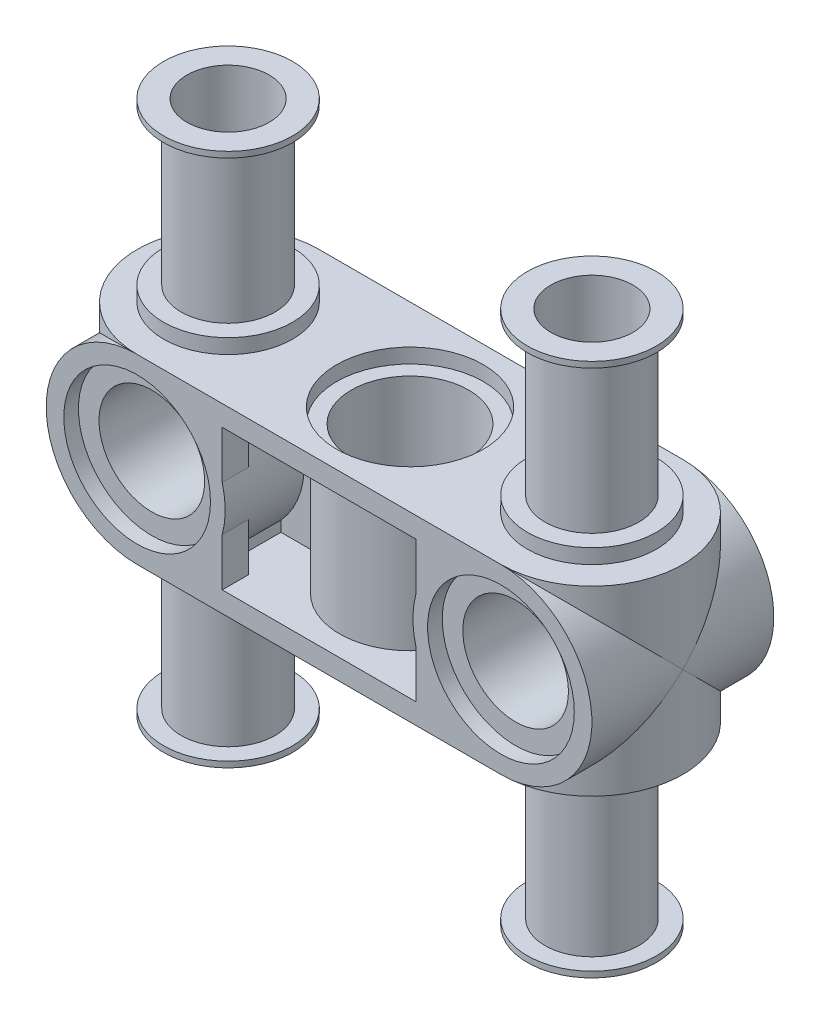
SolidWorks part; units mm, degrees
material "PVC Rigid"
ref_plane "Front Plane" through (0, 0, 0) normal (0, 0, 1) x (1, 0, 0)
ref_plane "Top Plane" through (0, 0, 0) normal (0, 1, 0) x (1, 0, 0)
ref_plane "Right Plane" through (0, 0, 0) normal (1, 0, 0) x (0, 0, -1)
sketch "Sketch1" plane through (0, 0, 0) normal (0, 1, 0) x (1, 0, 0)
  line L0 (-19.2625, 0) -> (26.4221, 0) construction
  line L1 (-7.874, 3.937) -> (7.874, 3.937)
  line L2 (0, 0) -> (0, 11.754) construction
  line L3 (7.874, -3.937) -> (-7.874, -3.937)
  circle A0 centre (-7.874, 0) radius 2.54 construction
  circle A1 centre (0, 0) radius 2.54 construction
  circle A2 centre (7.874, 0) radius 2.54 construction
  arc A3 (7.874, -3.937) -> (7.874, 3.937) centre (7.874, 0) ccw
  arc A4 (-7.874, 3.937) -> (-7.874, -3.937) centre (-7.874, 0) ccw
  dimension "D3" = 5.08
  dimension "D4" = 7.874
  dimension "D1" = 7.874
  dimension "D2" = 7.874
extrude "Extrude1" add sketch "Sketch1" along normal blind 3.937
sketch "Sketch2" plane through (0, 0, 0) normal (0, -1, 0) x (1, 0, 0)
  circle A0 centre (0, 0) radius 2.794
  dimension "D1" = 5.588
extrude "Cut-Extrude1" cut sketch "Sketch2" against normal blind 0.254
sketch "Sketch3" plane through (0, 0, 0) normal (0, -1, 0) x (1, 0, 0)
  circle A0 centre (7.874, 0) radius 2.794
  circle A1 centre (-7.874, 0) radius 2.794
  arc A2 (-7.874, 3.937) -> (-7.874, -3.937) centre (-7.874, 0) ccw construction
  arc A3 (7.874, -3.937) -> (7.874, 3.937) centre (7.874, 0) ccw construction
  dimension "D1" = 5.588
extrude "Extrude2" add sketch "Sketch3" along normal blind 0.635
sketch "Sketch5" plane through (0, -0.635, 0) normal (0, -1, 0) x (1, 0, 0)
  circle A0 centre (7.874, 0) radius 2.794 construction
  circle A1 centre (7.874, 0) radius 2.032
  circle A2 centre (-7.874, 0) radius 2.794 construction
  circle A3 centre (7.874, 0) radius 1.778
  circle A4 centre (-7.874, 0) radius 2.032
  circle A8 centre (-7.874, 0) radius 1.778
  dimension "D2" = 4.064
  dimension "D1" = 3.556
extrude "Extrude4" add sketch "Sketch5" along normal blind 6.985
sketch "Sketch6" plane through (0, -7.62, 0) normal (0, -1, 0) x (1, 0, 0)
  circle A1 centre (-7.874, 0) radius 1.778 construction
  circle A3 centre (7.874, 0) radius 1.778 construction
  circle A4 centre (-7.874, 0) radius 2.794 construction
  circle A5 centre (7.874, 0) radius 2.794 construction
  circle A6 centre (-7.874, 0) radius 2.794
  circle A7 centre (7.874, 0) radius 2.794
  circle A8 centre (7.874, 0) radius 1.778
  circle A9 centre (-7.874, 0) radius 1.778
extrude "Extrude5" add sketch "Sketch6" against normal blind 0.254
sketch "Sketch7" plane through (0, 0, -3.937) normal (0, 0, -1) x (-1, 0, 0)
  line L0 (-7.874, 3.937) -> (7.874, 3.937) construction
  line L2 (-7.874, 0) -> (7.874, 0) construction
  line L3 (-7.874, 0) -> (7.874, 0)
  line L4 (-7.874, 3.937) -> (7.874, 3.937)
  line L5 (-7.874, 3.937) -> (-11.811, 3.937)
  line L6 (7.874, 3.937) -> (11.811, 3.937)
  arc A0 (-11.811, 3.937) -> (-7.874, 0) centre (-7.874, 3.937) ccw
  arc A1 (7.874, 0) -> (11.811, 3.937) centre (7.874, 3.937) ccw
extrude "Extrude6" add sketch "Sketch7" against normal blind 7.874
sketch "Sketch8" plane through (0, 3.937, 0) normal (0, 1, 0) x (1, 0, 0)
  circle A0 centre (-7.874, 0) radius 2.54 construction
  circle A1 centre (0, 0) radius 2.54 construction
  circle A2 centre (7.874, 0) radius 2.54 construction
  circle A3 centre (-7.874, 0) radius 2.54 construction
  circle A4 centre (0, 0) radius 2.54
  circle A5 centre (7.874, 0) radius 2.54 construction
extrude "Cut-Extrude2" cut sketch "Sketch8" against normal blind 3.556
sketch "Sketch9" plane through (0, 0, 3.937) normal (0, 0, 1) x (1, 0, 0)
  circle A0 centre (7.874, 3.937) radius 2.286
  circle A1 centre (-7.874, 3.937) radius 2.286
  dimension "D1" = 4.572
extrude "Cut-Extrude3" cut sketch "Sketch9" against normal through all
sketch "Sketch10" plane through (0, 0, 3.937) normal (0, 0, 1) x (1, 0, 0)
  circle A0 centre (7.874, 3.937) radius 3.175
  circle A1 centre (-7.874, 3.937) radius 3.175
  dimension "D1" = 6.35
extrude "Cut-Extrude4" cut sketch "Sketch10" against normal blind 0.635
mirror "Mirror2" about plane through (0, 0, 0) normal (0, 0, 1) of "Cut-Extrude4"
sketch "Sketch11" plane through (0, 3.937, 0) normal (0, 1, 0) x (1, 0, 0)
  line L0 (-5.08, -0.508) -> (-5.08, -2.794)
  line L1 (5.08, 0.508) -> (5.08, 2.794)
  line L2 (5.08, -2.794) -> (5.08, -0.508)
  line L15 (-4.191, -3.429) -> (4.191, -3.429)
  line L23 (4.699, 3.937) -> (-4.699, 3.937) construction
  line L24 (-5.809, 0) -> (6.5071, 0) construction
  line L25 (-5.08, 0.508) -> (-3.0054, 0.508)
  line L26 (-5.809, 0.508) -> (6.5071, 0.508) construction
  line L27 (-5.08, -0.508) -> (-3.0054, -0.508)
  line L28 (-5.809, -0.508) -> (6.5071, -0.508) construction
  line L29 (-4.699, -3.937) -> (4.699, -3.937) construction
  line L30 (-4.191, -3.937) -> (4.191, -3.937)
  line L31 (3.0054, -0.508) -> (5.08, -0.508)
  line L32 (-4.191, -2.794) -> (-4.191, -3.429)
  line L34 (4.191, -3.429) -> (4.191, -2.794)
  line L35 (4.191, -2.794) -> (5.08, -2.794)
  line L36 (5.08, -2.794) -> (5.08, 2.794)
  line L37 (4.191, 3.429) -> (-4.191, 3.429)
  line L38 (4.191, 3.937) -> (-4.191, 3.937)
  line L39 (-4.191, 3.429) -> (-4.191, 2.794)
  line L40 (-5.08, 2.794) -> (-5.08, -2.794)
  line L41 (-5.08, -2.794) -> (-4.191, -2.794)
  line L42 (-4.191, -2.794) -> (-4.191, -3.937)
  line L43 (3.0054, 0.508) -> (5.08, 0.508)
  line L44 (4.191, -3.937) -> (4.191, -2.794)
  line L45 (4.191, -2.794) -> (5.08, -2.794)
  line L47 (-4.191, 3.937) -> (-4.191, 2.794)
  line L49 (-4.191, 2.794) -> (-5.08, 2.794)
  line L50 (-5.08, 2.794) -> (-5.08, 0.508)
  line L51 (-5.08, -2.794) -> (-4.191, -2.794)
  line L65 (-4.191, 2.794) -> (-5.08, 2.794)
  line L70 (5.08, 2.794) -> (4.191, 2.794)
  line L71 (5.08, 2.794) -> (4.191, 2.794)
  line L72 (4.191, 2.794) -> (4.191, 3.429)
  line L73 (4.191, 2.794) -> (4.191, 3.937)
  circle A5 centre (0, 0) radius 3.048
  arc A6 (-3.0054, -0.508) -> (3.0054, -0.508) centre (0, 0) ccw
  arc A8 (3.0054, 0.508) -> (-3.0054, 0.508) centre (0, 0) ccw
  dimension "D1" = 0.508
  dimension "D2" = 0.508
  dimension "D3" = 0.508
  dimension "D4" = 0.508
extrude "Cut-Extrude6" cut sketch "Sketch11" against normal blind 3.048
sketch "Sketch13" plane through (0, 0.381, 0) normal (0, 1, 0) x (1, 0, 0)
  circle A1 centre (0, 0) radius 2.54
  circle A2 centre (0, 0) radius 2.54
  dimension "D1" = 0
extrude "Cut-Extrude7" cut sketch "Sketch13" against normal through all
sketch "Sketch14" plane through (0, 0, 0) normal (0, -1, 0) x (1, 0, 0)
  circle A0 centre (0, 0) radius 3.175
  dimension "D1" = 6.35
extrude "Cut-Extrude8" cut sketch "Sketch14" against normal blind 0.635
sketch "Sketch17" plane through (0, 0, 3.937) normal (0, 0, 1) x (1, 0, 0)
  line L0 (-4.064, 3.937) -> (-4.699, 3.937)
  line L1 (-11.049, 3.937) -> (-11.684, 3.937)
  arc A0 (-11.684, 3.937) -> (-4.064, 3.937) centre (-7.874, 3.937) ccw
  arc A1 (-11.049, 3.937) -> (-4.699, 3.937) centre (-7.874, 3.937) ccw construction
  arc A2 (-11.049, 3.937) -> (-4.699, 3.937) centre (-7.874, 3.937) ccw
  dimension "D1" = 3.81
extrude "Extrude8" add sketch "Sketch17" against normal blind 7.112
mirror "Mirror3" about plane through (0, 0, 0) normal (1, 0, 0) of "Extrude8"
mirror "Mirror1" about plane through (-7.874, 3.937, 0) normal (0, 1, 0) of bodies 118 111
